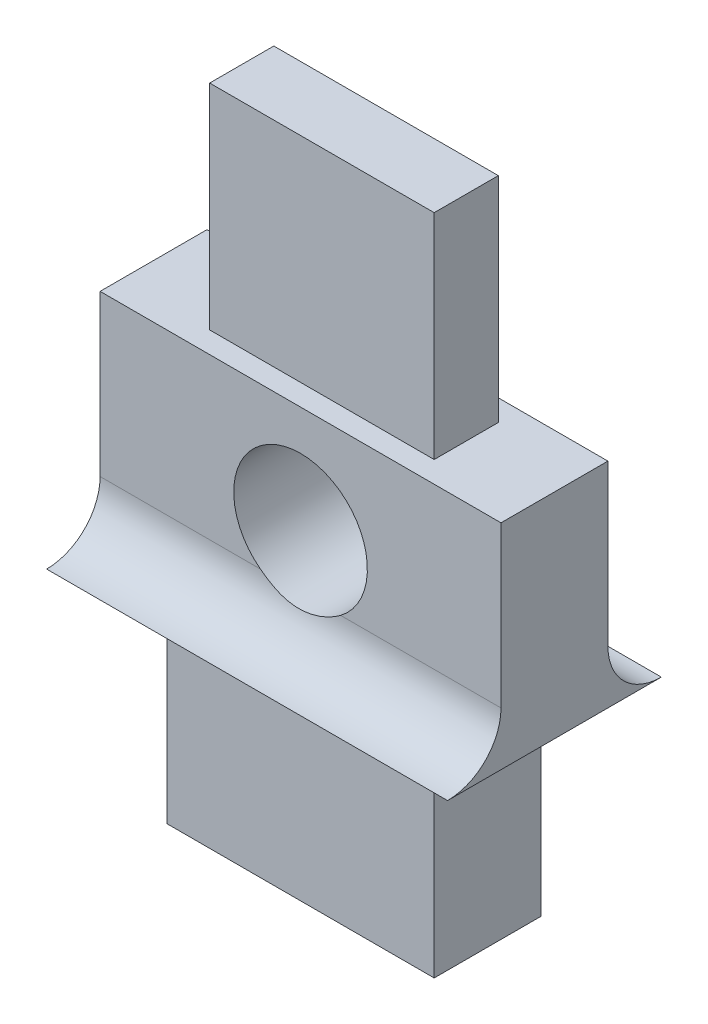
SolidWorks part; units mm, degrees
ref_plane "Front Plane" through (0, 0, 0) normal (0, 0, 1) x (1, 0, 0)
ref_plane "Top Plane" through (0, 0, 0) normal (0, 1, 0) x (1, 0, 0)
ref_plane "Right Plane" through (0, 0, 0) normal (1, 0, 0) x (0, 0, -1)
sketch "Sketch1" plane through (0, 0, 0) normal (0, 0, 1) x (1, 0, 0)
  line L0 (1952.1768, 1466.8841) -> (1957.1768, 1466.8841)
  line L1 (1952.1768, 1454.8841) -> (1957.1768, 1454.8841)
  line L3 (1957.1768, 1458.8841) -> (1957.1768, 1454.8841)
  line L4 (1957.1768, 1458.8841) -> (1958.4268, 1458.8841)
  line L5 (1958.4268, 1462.8841) -> (1958.4268, 1458.8841)
  line L6 (1957.1768, 1462.8841) -> (1957.1768, 1466.8841)
  line L7 (1957.1768, 1462.8841) -> (1958.4268, 1462.8841)
  line L37 (1952.1768, 1458.8841) -> (1950.9268, 1458.8841)
  line L40 (1952.1768, 1458.8841) -> (1952.1768, 1454.8841)
  line L127 (1952.1768, 1462.8841) -> (1950.9268, 1462.8841)
  line L130 (1952.1768, 1462.8841) -> (1952.1768, 1466.8841)
  line L131 (1950.9268, 1462.8841) -> (1950.9268, 1458.8841)
  circle A82 centre (1954.6768, 1460.8841) radius 1.25
  dimension "D1" = 2.5
  dimension "D2" = 1950.9268
  dimension "D3" = 1954.6768
  dimension "D4" = 1957.1768
  dimension "D5" = 1454.8841
  dimension "D6" = 1458.8841
  dimension "D7" = 1460.8841
extrude "Boss-Extrude1" add sketch "Sketch1" along normal blind 2
sketch "Sketch2" plane through (1950.9268, 0, 0) normal (-1, 0, 0) x (0, 0, 1)
  line L0 (1, 1454.8841) -> (1, 1461.8841) construction
  line L1 (2, 1458.8841) -> (2, 1459.8841)
  line L2 (2, 1458.8841) -> (3, 1458.8841)
  line L3 (0, 1458.8841) -> (-1, 1458.8841)
  line L4 (0, 1458.8841) -> (0, 1459.8841)
  arc A0 (2, 1459.8841) -> (3, 1458.8841) centre (3, 1459.8841) ccw
  arc A1 (0, 1459.8841) -> (-1, 1458.8841) centre (-1, 1459.8841) cw
  dimension "D1" = 1
  dimension "D2" = 1
  dimension "D3" = 4
  dimension "D4" = 1
  dimension "D5" = 4
  dimension "D6" = 2
extrude "Boss-Extrude2" add sketch "Sketch2" against normal up to surface (7.5 mm away) up to face at (1958.4268, 1460.8841, 1)
sketch "Sketch3" plane through (0, 0, 2) normal (0, 0, 1) x (1, 0, 0)
  circle A0 centre (1954.6768, 1460.8841) radius 1.25
  dimension "D1" = 2.5
extrude "Cut-Extrude1" cut sketch "Sketch3" against normal through all both and the other way through all
sketch "Sketch4" plane through (0, 1466.8841, 0) normal (0, 1, 0) x (1, 0, 0)
  line L1 (1952.1768, -2) -> (1957.1768, -2)
  line L2 (1952.1768, -2) -> (1952.1768, 0)
  line L3 (1952.1768, 0) -> (1957.1768, 0)
  line L4 (1957.1768, -2) -> (1957.1768, 0)
  line L5 (1952.5768, -1.6) -> (1956.7768, -1.6)
  line L6 (1952.5768, -1.6) -> (1952.5768, -0.4)
  line L7 (1952.5768, -0.4) -> (1956.7768, -0.4)
  line L8 (1956.7768, -1.6) -> (1956.7768, -0.4)
  dimension "D1" = 0.4
  dimension "D2" = 0.4
  dimension "D3" = 0.4
  dimension "D4" = 0.4
extrude "Cut-Extrude2" cut sketch "Sketch4" against normal blind 4
equation "\"D4@Sketch4\"=\"tol2@parametersSketch@prostheticParameters.SLDPRT\""
equation "\"D3@Sketch4\"=\"tol2@parametersSketch@prostheticParameters.SLDPRT\""
equation "\"D2@Sketch4\"=\"tol2@parametersSketch@prostheticParameters.SLDPRT\""
equation "\"D1@Sketch4\"=\"tol2@parametersSketch@prostheticParameters.SLDPRT\""
